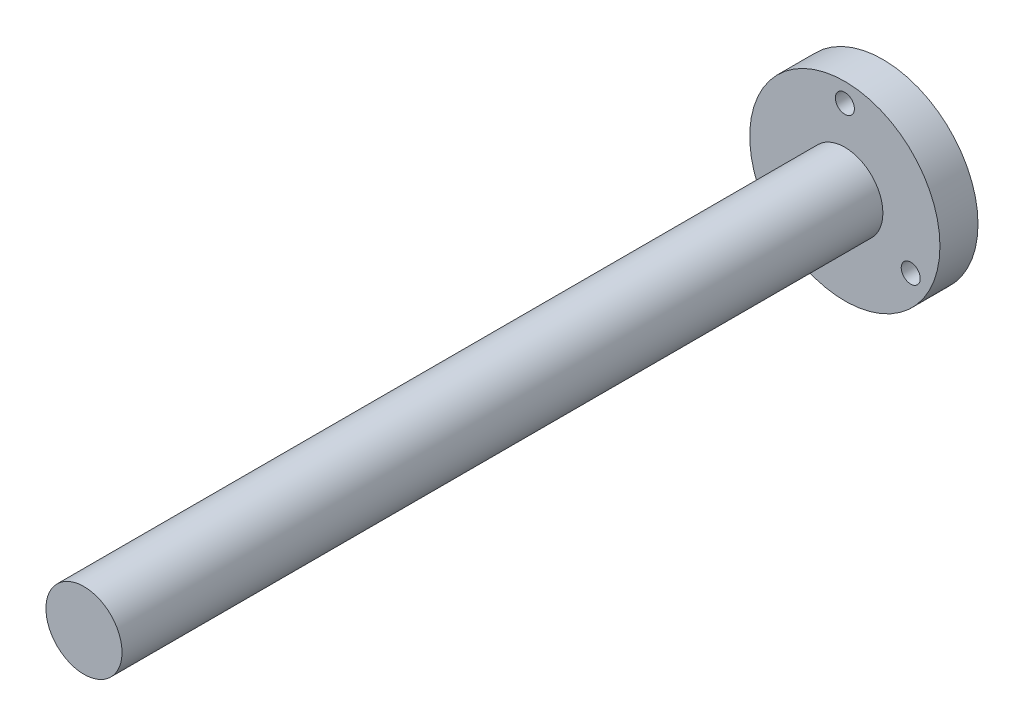
SolidWorks part; units mm, degrees
ref_plane "Front Plane" through (0, 0, 0) normal (0, 0, 1) x (1, 0, 0)
ref_plane "Top Plane" through (0, 0, 0) normal (0, 1, 0) x (1, 0, 0)
ref_plane "Right Plane" through (0, 0, 0) normal (1, 0, 0) x (0, 0, -1)
sketch "Sketch1" plane through (0, 0, 0) normal (0, 0, 1) x (1, 0, 0)
  circle A0 centre (0, 0) radius 25
  circle A1 centre (0, 20) radius 2.5
  circle A2 centre (17.3205, -10) radius 2.5
  circle A3 centre (-17.3205, -10) radius 2.5
  dimension "D1" = 50
  dimension "D2" = 5
  dimension "D4" = 20
  dimension "D3" = 3
extrude "Boss-Extrude1" add sketch "Sketch1" along normal blind 10
sketch "Sketch2" plane through (0, 0, 10) normal (0, 0, 1) x (1, 0, 0)
  circle A0 centre (0, 0) radius 10
  dimension "D1" = 20
extrude "Boss-Extrude2" add sketch "Sketch2" along normal blind 200
